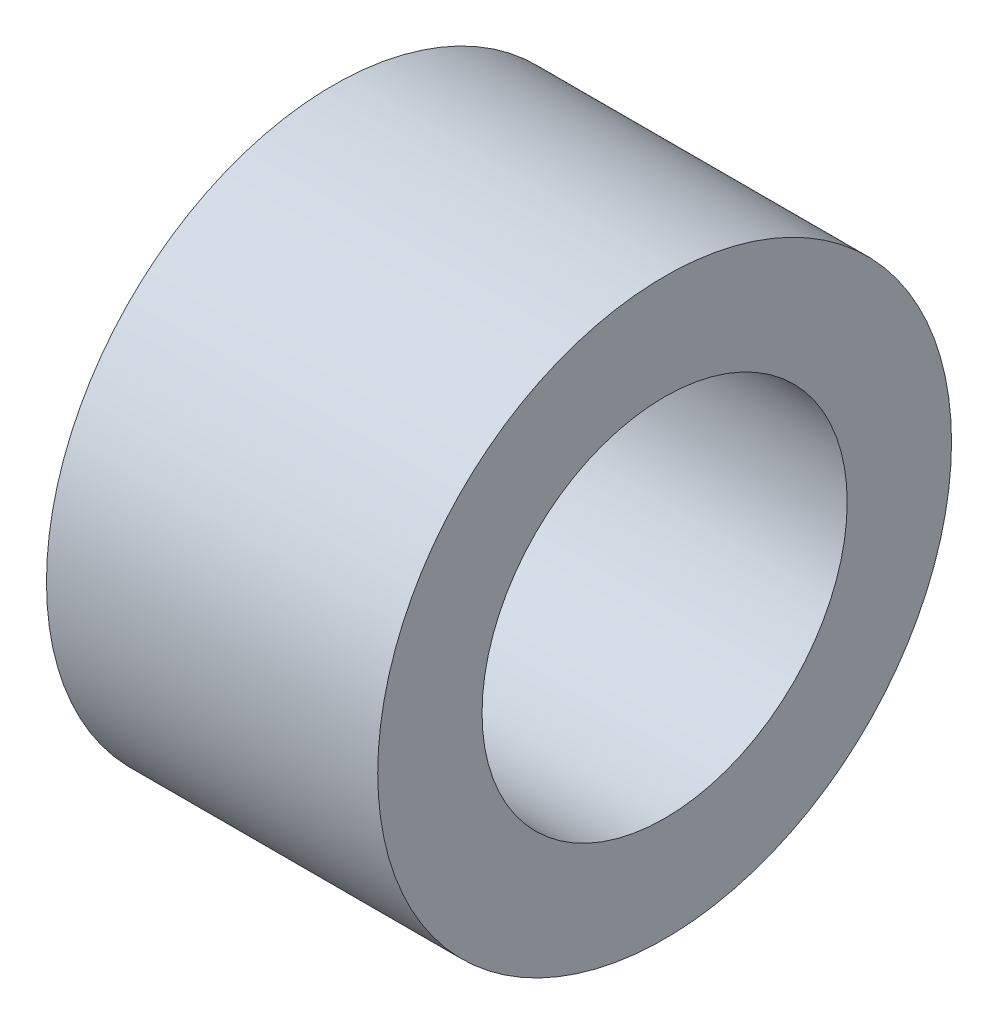
SolidWorks part; units mm, degrees
ref_plane "Front Plane" through (0, 0, 0) normal (0, 0, 1) x (1, 0, 0)
ref_plane "Top Plane" through (0, 0, 0) normal (0, 1, 0) x (1, 0, 0)
ref_plane "Right Plane" through (0, 0, 0) normal (1, 0, 0) x (0, 0, -1)
sketch "Leg_Spring Sketch" plane through (0, 0, 0) normal (0, 0, 1) x (1, 0, 0)
  line L0 (-3000, 0) -> (3000, 0) construction
  line L1 (0, 7) -> (12.7, 7)
  line L2 (12.7, 7) -> (12.7, 11)
  line L3 (12.7, 11) -> (0, 11)
  line L4 (0, 11) -> (0, 7)
revolve "Leg_Spring" add sketch "Leg_Spring Sketch" angle 360 about L0
ref_axis "Engine Axis" through (13.335, 0, 0) along (-1, 0, 0)
